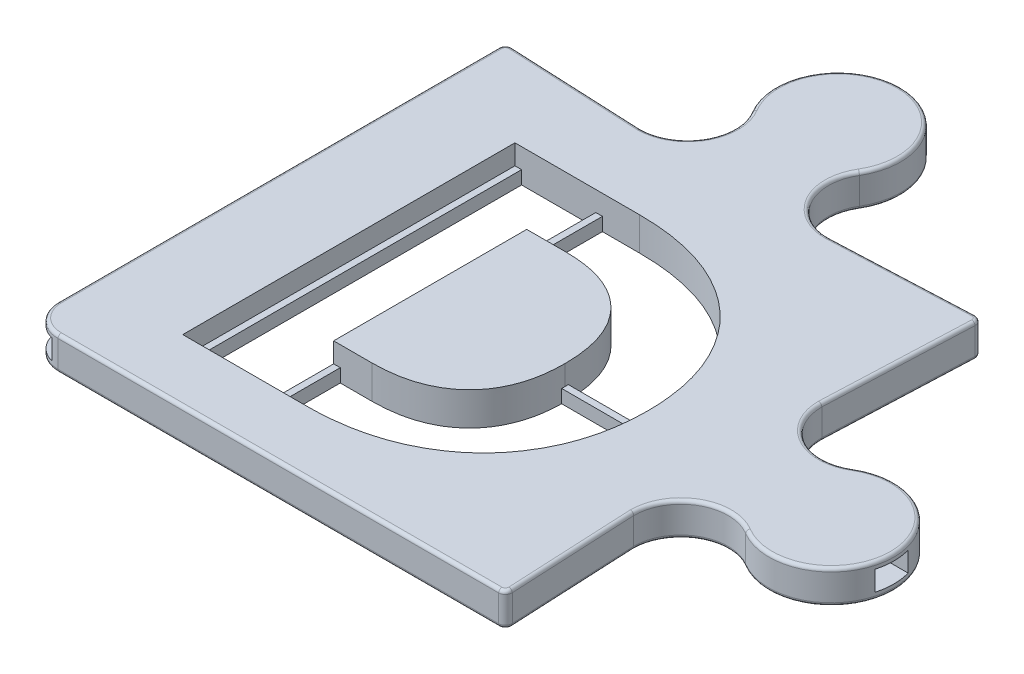
SolidWorks part; units mm, degrees
ref_plane "Front Plane" through (0, 0, 0) normal (0, 0, 1) x (1, 0, 0)
ref_plane "Top Plane" through (0, 0, 0) normal (0, 1, 0) x (1, 0, 0)
ref_plane "Right Plane" through (0, 0, 0) normal (1, 0, 0) x (0, 0, -1)
sketch "Sketch1" plane through (0, 0, 0) normal (0, 1, 0) x (1, 0, 0)
  line L0 (-31, -36) -> (37, -36) construction
  line L1 (-36, 37) -> (-36, -31) construction
  line L2 (-14.1421, 36) -> (-36, 37) construction
  line L3 (37, 37) -> (14.1421, 36) construction
  line L4 (36, 13.1421) -> (37, 37) construction
  line L5 (37, -36) -> (36, -15.1421) construction
  line L6 (-35.4, 36.3719) -> (-35.4, -31)
  line L7 (-36, 36) -> (36, 36) construction
  line L8 (-36, 36) -> (-36, -36) construction
  line L9 (-36, -36) -> (36, -36) construction
  line L10 (36, 36) -> (36, -36) construction
  line L11 (-31, -35.4) -> (36.3705, -35.4)
  line L12 (36.3705, -35.4) -> (35.4, -15.1568)
  line L13 (35.4, 13.155) -> (36.3732, 36.372)
  line L14 (36.3732, 36.372) -> (14.1555, 35.4)
  line L15 (-14.1562, 35.4) -> (-35.4, 36.3719)
  line L16 (-30, -24) -> (30, -24) construction
  line L17 (-30, 29) -> (30, 29) construction
  line L18 (-30, 29) -> (-30, -31) construction
  line L19 (-30, -31) -> (30, -31) construction
  line L20 (30, 29) -> (30, -31) construction
  line L21 (-30, 24) -> (30, 24) construction
  line L22 (-30, 24) -> (-30, -26) construction
  line L23 (-30, -26) -> (30, -26) construction
  line L24 (30, 24) -> (30, -26) construction
  arc A0 (-36, -31) -> (-31, -36) centre (-31, -31) ccw construction
  arc A1 (-14.1421, 36) -> (-8.571, 45.8485) centre (-14.1421, 42.5) ccw construction
  arc A2 (8.571, 45.8485) -> (-8.571, 45.8485) centre (0, 51) ccw construction
  arc A3 (8.571, 45.8485) -> (14.1421, 36) centre (14.1421, 42.5) ccw construction
  arc A4 (36, 13.1421) -> (45.8485, 7.571) centre (42.5, 13.1421) ccw construction
  arc A5 (45.8485, -9.571) -> (45.8485, 7.571) centre (51, -1) ccw construction
  arc A6 (45.8485, -9.571) -> (36, -15.1421) centre (42.5, -15.1421) ccw construction
  arc A7 (-35.4, -31) -> (-31, -35.4) centre (-31, -31) ccw
  arc A8 (46.1576, -9.0567) -> (35.4, -15.1568) centre (42.5, -15.1421) ccw
  arc A9 (46.1576, -9.0567) -> (46.1576, 7.0567) centre (51, -1) ccw
  arc A10 (35.4, 13.155) -> (46.1576, 7.0567) centre (42.5, 13.1421) ccw
  arc A11 (8.0567, 46.1576) -> (14.1555, 35.4) centre (14.1421, 42.5) ccw
  arc A12 (8.0567, 46.1576) -> (-8.0567, 46.1576) centre (0, 51) ccw
  arc A13 (-14.1562, 35.4) -> (-8.0567, 46.1576) centre (-14.1421, 42.5) ccw
  point P32 (36, 0)
  point P34 (0, 36)
  dimension "D5" = 6.5
  dimension "D6" = 10
  dimension "D7" = 6.5
  dimension "D13" = 5
  dimension "D9" = 10
  dimension "D11" = 6.5
  dimension "D12" = 6.5
  dimension "D1" = 72
  dimension "D2" = 1
  dimension "D3" = 1
  dimension "D4" = 15
  dimension "D8" = 1
  dimension "D10" = 35
  dimension "D14" = 15
  dimension "D15" = 36
  dimension "D16" = 1
  dimension "D18" = 60
  dimension "D19" = 60
  dimension "D20" = 5
  dimension "D21" = 6
  dimension "D22" = 5
  dimension "D23" = 50
  dimension "D24" = 2
  dimension "D17" = 0.6
extrude "Boss-Extrude1" add sketch "Sketch1" along normal blind 5
sketch "Sketch6" plane through (0, 0, 0) normal (0, -1, 0) x (1, 0, 0)
  line L0 (-35.4, -36.3719) -> (-35.4, 31) construction
  line L1 (-35.4, 17.9) -> (-27.4, 17.9)
  line L2 (-35.4, 17.9) -> (-35.4, -16.1)
  line L3 (-35.4, -16.1) -> (-27.4, -16.1)
  line L4 (-27.4, 17.9) -> (-27.4, -16.1)
  line L5 (-31, 35.4) -> (36.3705, 35.4) construction
  line L6 (-35.4, 14.65) -> (-30.4, 14.65)
  line L7 (-35.4, 14.65) -> (-35.4, -12.85)
  line L8 (-35.4, -12.85) -> (-30.4, -12.85)
  line L9 (-30.4, 14.65) -> (-30.4, -12.85)
  point P15 (-27.4, 0.9)
  point P16 (-30.4, 0.9)
  line M28 (-35.4, 31) -> (-35.4, -36.3719)
  dimension "D1" = 8
  dimension "D2" = 20.75
  dimension "D3" = 27.5
  dimension "D4" = 5
  dimension "D5" = 34
extrude "Cut-Extrude3" cut sketch "Sketch6" against normal blind 3 from offset 1 contours L6 L9 L8 L3 L4 L1 M28 | L9 L6 L2 L8 region at (-29.8665, 0, 0.9) region at (-32.9, 0, 0.9) offset against normal yes
extrude "Cut-Extrude4" cut sketch "Sketch6<3>" against normal up to next contours L9 L6 L2 L8 region at (-32.9, 0, 0.9)
sketch "Sketch6<3>" plane through (0, 0, 0) normal (0, -1, 0) x (1, 0, 0) same geometry as "Sketch6"
sketch "Sketch8" plane through (0, 0, 0) normal (0, -1, 0) x (1, 0, 0)
  line L1 (-2.5, -51.4) -> (2.5, -51.4)
  line L2 (-2.5, -51.4) -> (-2.5, -60.4)
  line L3 (-2.5, -60.4) -> (2.5, -60.4)
  line L4 (2.5, -51.4) -> (2.5, -60.4)
  line L5 (51.4, 3.5) -> (60.4, 3.5)
  line L6 (51.4, 3.5) -> (51.4, -1.5)
  line L7 (51.4, -1.5) -> (60.4, -1.5)
  line L8 (60.4, 3.5) -> (60.4, -1.5)
  arc A0 (-8.0567, -46.1576) -> (8.0567, -46.1576) centre (0, -51) ccw construction
  arc A1 (46.1576, -7.0567) -> (46.1576, 9.0567) centre (51, 1) ccw construction
  point P4 (0, -60.4)
  point P13 (60.4, 1)
  dimension "D1" = 5
  dimension "D2" = 9
  dimension "D3" = 5
  dimension "D4" = 9
extrude "Cut-Extrude5" cut sketch "Sketch8" against normal blind 3 from offset 1 offset against normal yes
sketch "Sketch9" plane through (0, 0, 0) normal (0, -1, 0) x (1, 0, 0)
  line L0 (-31, 35.4) -> (36.3705, 35.4) construction
  line L1 (-35.4, 14.65) -> (-35.4, 31) construction
  line L2 (-31.7636, 35.3332) -> (-35.4, 31) construction
  line L3 (-33.2571, 29.735) -> (-30.0429, 33.565) construction
  line L4 (-30.0429, 33.565) -> (-33.2571, 29.735) construction
  line L5 (-30.0429, 33.565) -> (-32.7119, 35.8048)
  line L6 (-33.2571, 29.735) -> (-35.926, 31.9747)
  line L7 (-32.7119, 35.8048) -> (-35.926, 31.9747)
  circle A0 centre (-31.65, 31.65) radius 2.5
  arc A1 (-31, 35.4) -> (-35.4, 31) centre (-31, 31) ccw construction
  arc M41 (-31, 35.4) -> (-35.4, 31) centre (-31, 31) ccw
  dimension "D1" = 5
  dimension "D3" = 3.75
  dimension "D4" = 5.6569
  dimension "D2" = 3.75
extrude "Cut-Extrude6" cut sketch "Sketch9" against normal blind 3 from offset 1 contours A0 L5 L6 M41 | A0 L5 region at (-33.6239, 0, 33.3064) region at (-31.65, 0, 31.65) offset against normal yes
sketch "Sketch11" plane through (-35.4, 0, 0) normal (-1, 0, 0) x (0, 0, 1)
  line L0 (-13.155, 0) -> (-36.372, 0) construction
  line L1 (-25.1, 3) -> (-19.1, 3)
  line L2 (-25.1, 3) -> (-25.1, 1.5)
  line L3 (-25.1, 1.5) -> (-19.1, 1.5)
  line L4 (-19.1, 3) -> (-19.1, 1.5)
  line L5 (-16.1, 4) -> (-16.1, 1) construction
  line L6 (35.4, 0) -> (15.1568, 0) construction
  line L7 (20.9, 3) -> (26.9, 3)
  line L8 (20.9, 3) -> (20.9, 1.5)
  line L9 (20.9, 1.5) -> (26.9, 1.5)
  line L10 (26.9, 3) -> (26.9, 1.5)
  line L12 (17.9, 4) -> (17.9, 1) construction
  dimension "D1" = 3
  dimension "D2" = 1.5
  dimension "D3" = 3
  dimension "D4" = 6
  dimension "D5" = 3
  dimension "D6" = 1.5
  dimension "D7" = 6
  dimension "D8" = 3
fillet "Fillet1" radius 0.5 17 edges at (-35.4, 0, 22.825) (-34.1113, 0, 34.1113) (2.6853, 0, 35.4) (35.8853, 0, 25.2784) (38.9978, 0, 8.966) (60.4, 0, 1) (38.9986, 0, -6.9655) (35.8866, 0, -24.7635) (25.2643, 0, -35.886) (7.9657, 0, -38.9984) (0, 0, -60.4) (-7.9658, 0, -38.9981) (-24.7781, 0, -35.886) (-35.4, 0, -24.611) (-32.9, 0, -12.85) (-30.4, 0, 0.9) (-32.9, 0, 14.65)
fillet "Fillet2" radius 0.5 13 edges at (-7.9658, 5, -38.9981) (0, 5, -60.4) (7.9657, 5, -38.9984) (25.2643, 5, -35.886) (35.8866, 5, -24.7635) (38.9986, 5, -6.9655) (60.4, 5, 1) (38.9978, 5, 8.966) (35.8853, 5, 25.2784) (2.6853, 5, 35.4) (-34.1113, 5, 34.1113) (-35.4, 5, -2.686) (-24.7781, 5, -35.886)
fillet "Fillet3" radius 1 9 edges at (36.2202, 0.1464, -36.2187) (36.2202, 4.8536, -36.2187) (36.3732, 2.5, -36.372) (-35.2536, 0.1464, -36.2186) (-35.2536, 4.8536, -36.2186) (36.2169, 0.1464, 35.2536) (36.2169, 4.8536, 35.2536) (36.3705, 2.5, 35.4) (-35.4, 2.5, -36.3719)
extrude "Cut-Extrude9" cut sketch "Sketch11" against normal blind 3
chamfer "Chamfer1" distance 1 angle 50 2 edges at (-35.4, 1.5, 23.9) (-35.4, 1.5, -22.1) first distance on face at (-35.4, 2.25, -22.1)
sketch "Sketch12" plane through (0, 5, 0) normal (0, 1, 0) x (1, 0, 0)
  text T0 "D" font "Poppins" height 50
extrude "Cut-Extrude10" cut sketch "Sketch12" against normal through all
sketch "Sketch13" plane through (0, 0, 0) normal (0, -1, 0) x (1, 0, 0)
  line L0 (-9.46, 15.458) -> (-3.6892, 15.458) construction
  line L1 (-8.46, 15.458) -> (-9.46, 15.458)
  line L2 (-8.46, 15.458) -> (-8.46, 26)
  line L3 (-8.46, 26) -> (-9.46, 26)
  line L4 (-9.46, 15.458) -> (-9.46, 26)
  line L5 (-2.906, 26) -> (-21.6303, 26) construction
  line L6 (-3.6892, -13.6022) -> (-9.46, -13.6022) construction
  line L7 (-8.46, -13.6022) -> (-9.46, -13.6022)
  line L8 (-8.46, -13.6022) -> (-8.46, -24)
  line L9 (-8.46, -24) -> (-9.46, -24)
  line L10 (-9.46, -13.6022) -> (-9.46, -24)
  line L11 (-21.6303, -24) -> (-2.906, -24) construction
  line L12 (10.913, 1) -> (23.31, 1) construction
  line L14 (10.3507, 1.5038) -> (23.8847, 1.5038)
  line L15 (10.3507, 1.5038) -> (10.3507, 0.5038)
  line L16 (10.3507, 0.5038) -> (23.8847, 0.5038)
  line L17 (23.8847, 1.5038) -> (23.8847, 0.5038)
  line L18 (-21.6303, 26) -> (-20.6303, 26)
  line L19 (-21.6303, 26) -> (-21.6303, -24)
  line L20 (-21.6303, -24) -> (-20.6303, -24)
  line L21 (-20.6303, 26) -> (-20.6303, -24)
  dimension "D1" = 1
  dimension "D2" = 1
  dimension "D3" = 1
  dimension "D4" = 1
extrude "Boss-Extrude6" add sketch "Sketch13" against normal blind 2
